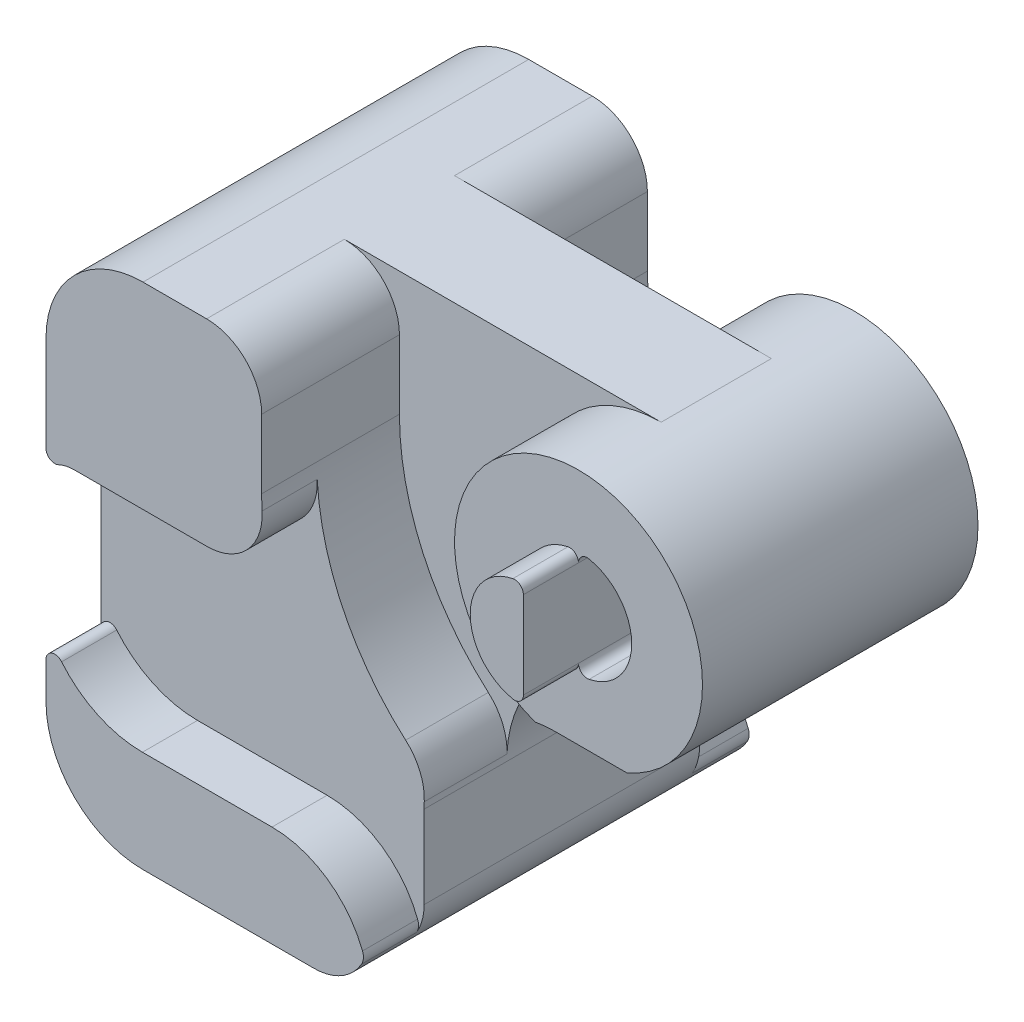
SolidWorks part; units mm, degrees
material "ABS"
ref_plane "Front Plane" through (0, 0, 0) normal (0, 0, 1) x (1, 0, 0)
ref_plane "Top Plane" through (0, 0, 0) normal (0, 1, 0) x (1, 0, 0)
ref_plane "Right Plane" through (0, 0, 0) normal (1, 0, 0) x (0, 0, -1)
sketch "Sketch1" plane through (0, 0, 0) normal (0, 0, 1) x (1, 0, 0)
  line L0 (5.5562, 0) -> (16.6687, 0)
  line L1 (0, 5.5562) -> (22.225, 5.5562)
  line L4 (22.225, 5.5562) -> (22.225, -5.5562) construction
  line L5 (0, 5.5562) -> (22.225, 5.5562) construction
  line L9 (13.1316, 0.7956) -> (22.225, 0) construction
  line L10 (22.225, 0) -> (22.225, -9.1281) construction
  line L11 (5.5562, 0) -> (0, 0)
  line L12 (0, 0) -> (0, 5.5562)
  line L13 (13.7542, 7.9121) -> (13.1316, 0.7956) construction
  circle A0 centre (0, 0) radius 5.5562 construction
  circle A1 centre (22.225, 0) radius 5.5562 construction
  circle A2 centre (22.225, -9.1281) radius 3.5719
  arc A3 (22.225, -5.5562) -> (22.225, 5.5562) centre (22.225, 0) ccw
  circle A5 centre (22.225, 0) radius 1.7859
  circle A6 centre (22.225, -9.1281) radius 1.7859
  arc A7 (16.6687, 0) -> (22.225, -5.5562) centre (22.225, 0) ccw
  circle A23 centre (22.225, 0) radius 9.1281 construction
  circle A30 centre (2.7781, 2.7781) radius 2.7781
  circle A31 centre (0.8137, 4.7426) radius 0.8137
  circle A32 centre (13.1316, 0.7956) radius 1.7859
  circle A33 centre (13.1316, 0.7956) radius 3.5719
  circle A34 centre (13.7542, 7.9121) radius 1.7859
  circle A35 centre (13.7542, 7.9121) radius 3.5719
  arc A36 (14.9108, 0.6399) -> (22.225, -7.3422) centre (22.225, 0) ccw
  arc A37 (22.225, -10.9141) -> (11.3525, 0.9512) centre (22.225, 0) cw
  arc A38 (22.225, -12.7) -> (9.5733, 1.1069) centre (22.225, 0) cw
  dimension "D1" = 22.225
  dimension "D2" = 11.1125
  dimension "D3" = 3.5719
  dimension "D5" = 7.1437
  dimension "D4" = 95
sketch "Sketch3" plane through (0, 0, 0) normal (0, 0, 1) x (1, 0, 0)
  line L0 (0.8137, 5.5562) -> (11.0694, 5.5562)
  line L1 (0, 5.5562) -> (22.225, 5.5562) construction
  line L2 (0, 5.5562) -> (0, 0)
  line L3 (0, 0) -> (9.6495, 0)
  line L4 (5.5562, 0) -> (16.6687, 0) construction
  line L5 (13.1316, 4.6214) -> (15.1433, 4.6214)
  line L7 (0, 0) -> (0, -3.175)
  line L8 (0, -3.175) -> (9.6495, -3.175)
  line L9 (9.6495, -3.175) -> (9.6495, 0)
  line L10 (0, 5.5562) -> (0.8137, 5.5562)
  line L11 (0, 5.5562) -> (0, 11.484)
  line L12 (0, 11.484) -> (13.7542, 11.484)
  line L13 (9.3057, 0.7956) -> (9.3057, -3.175)
  circle A0 centre (13.1316, 0.7956) radius 3.5719
  circle A1 centre (13.7542, 7.9121) radius 3.5719
  circle A2 centre (13.7542, 7.9121) radius 1.5321
  circle A3 centre (13.1316, 0.7956) radius 3.5719 construction
  circle A5 centre (13.7542, 7.9121) radius 3.5719 construction
  circle A6 centre (0.8137, 4.7426) radius 0.8137 construction
  circle A9 centre (13.1316, 0.7956) radius 3.8259
  arc A11 (9.5733, 1.1069) -> (9.6495, -1.7736) centre (22.225, 0) ccw
  dimension "D2" = 3.0643
  dimension "D3" = 0.254
  dimension "D1" = 3.175
extrude "Boss-Extrude1" add sketch "Sketch3" along normal blind 5.5562 contours A1 L12 L11 L10 L0 | A2 | A9 L5 A1 A2 | A9 A1 L0 L10 L2 L3 L13 | L13 L3 L7 L8 region at (5.3993, 8.5885, 0) region at (5.1753, 2.918, 0) region at (10.5911, 9.3448, 0) region at (4.6529, -1.5875, 0) region at (13.7542, 7.9121, 0)
sketch "Sketch5" plane through (0, 0, 5.5562) normal (0, 0, 1) x (1, 0, 0)
  line L0 (13.7542, 11.484) -> (0, 11.484)
  line L1 (0, 11.484) -> (0, -3.175)
  line L2 (0, -3.175) -> (9.3057, -3.175)
  line L3 (9.3057, -3.175) -> (9.3057, 0.7956)
  line L4 (13.7542, 9.4443) -> (13.7542, 6.38)
  line L7 (0, 0) -> (9.3057, 0) construction
  line L8 (6.2136, 7.9121) -> (10.1824, 7.9121)
  line L9 (6.2136, 7.9121) -> (6.2136, 11.484)
  line L10 (6.2136, 11.484) -> (10.1824, 11.484)
  line L11 (10.1824, 7.9121) -> (10.1824, 11.484)
  line L12 (5.5562, 0) -> (16.6687, 0) construction
  line L13 (0, 5.5562) -> (6.5911, 5.5562) construction
  line L14 (0, 5.5562) -> (22.225, 5.5562) construction
  line L15 (0, -0.254) -> (9.3057, -0.254)
  line L16 (0, 5.8102) -> (6.5125, 5.8102)
  circle A0 centre (13.7542, 7.9121) radius 3.5719
  circle A1 centre (13.1316, 0.7956) radius 3.8259
  circle A2 centre (13.7542, 7.9121) radius 1.5321
  arc A5 (13.1316, 4.6214) -> (9.3057, 0.7956) centre (13.1316, 0.7956) ccw construction
  circle A6 centre (13.7542, 7.9121) radius 7.5406
  circle A7 centre (0.8137, 4.7426) radius 0.8137 construction
  circle A8 centre (2.7781, 2.7781) radius 2.7781 construction
  circle A9 centre (2.7781, 2.7781) radius 2.7781 construction
  circle A10 centre (0.8137, 4.7426) radius 0.8137 construction
  circle A11 centre (2.7781, 2.7781) radius 3.0321
  circle A12 centre (0.8137, 4.7426) radius 1.0677
  circle A14 centre (13.7542, 7.9121) radius 1.5321 construction
  arc M5 (9.3057, 0.7956) -> (13.1316, 4.6214) centre (13.1316, 0.7956) cw
  line M6 (13.1316, 4.6214) -> (15.1433, 4.6214)
  arc M7 (15.1433, 4.6214) -> (13.7542, 11.484) centre (13.7542, 7.9121) ccw
  line M8 (13.7542, 11.484) -> (0, 11.484)
  line M9 (0, 11.484) -> (0, -3.175)
  dimension "D2" = 3.9688
  dimension "D3" = 0.254
  dimension "D4" = 0.254
extrude "Cut-Extrude1" cut sketch "Sketch5" against normal blind 1.5875 contours A12 A11 M9 | A11 L15 L3 A6 L16 M5 | A12 A11 L16 | A11 A12 | A11 A12 M9 | A0 A2 M7 M5 M6 | A0 L11 M8 | A12 L1 A11 | A2 | A2 region at (10.9802, 10.6862, 5.5562) region at (16.2096, 10.3675, 5.5562) region at (6.775, 2.189, 5.5562) region at (1.6647, 5.7301, 5.5562) region at (2.9672, 2.6346, 5.5562) region at (0.5308, 5.2179, 5.5562) region at (1.0613, 4.4949, 5.5562) region at (0.0057, 4.0253, 5.5562)
extrude "Cut-Extrude2" cut sketch "Sketch5<5>" against normal blind 3.9688 contours L8 A6 A1 A0 | L0 A6 L8 L11 | A6 L10 L9 | A0 L11 M8 region at (10.9802, 10.6862, 5.5562) region at (8.3345, 9.6262, 5.5562) region at (8.843, 5.3762, 5.5562) region at (6.4805, 10.602, 5.5562)
sketch "Sketch5<5>" plane through (0, 0, 5.5562) normal (0, 0, 1) x (1, 0, 0) same geometry as "Sketch5"
extrude "Cut-Extrude3" cut sketch "Sketch5<6>" against normal through all contours L4 A2 region at (14.4045, 7.9121, 5.5562)
sketch "Sketch5<6>" plane through (0, 0, 5.5562) normal (0, 0, 1) x (1, 0, 0) same geometry as "Sketch5"
mirror "Mirror1" about plane through (0, 0, 0) normal (0, 0, 1) of "Boss-Extrude1", "Cut-Extrude1", "Cut-Extrude2", "Cut-Extrude3"
fillet "Fillet1" radius 2.794 4 edges at (0, 11.484, 0) (0, -3.175, 0) (9.3057, -0.254, -4.7625) (9.3057, -0.254, 4.7625)
fillet "Fillet6" radius 1.5875 1 edges at (9.3057, -3.175, 0)
fillet "Fillet2" radius 1.5875 5 edges at (9.4239, 1.7389, -2.7781) (9.4239, 1.7389, 2.7781) (6.2136, 11.484, -3.5719) (6.2136, 11.484, 3.5719) (6.5125, 5.8102, 4.7625)
fillet "Fillet4" radius 0.254 6 edges at (0, 1.5633, -4.7625) (0, 1.5633, 4.7625) (0, 5.4338, -4.7625) (0, 5.4338, 4.7625) (13.7542, 6.38, 4.7625) (13.7542, 9.4443, 4.7625)
fillet "Fillet5" radius 0.254 2 edges at (13.7542, 6.38, 0) (13.7542, 9.4443, 0)
fillet "Fillet7" radius 0.3969 2 edges at (9.1777, -2.212, -4.7625) (9.1777, -2.212, 4.7625)
